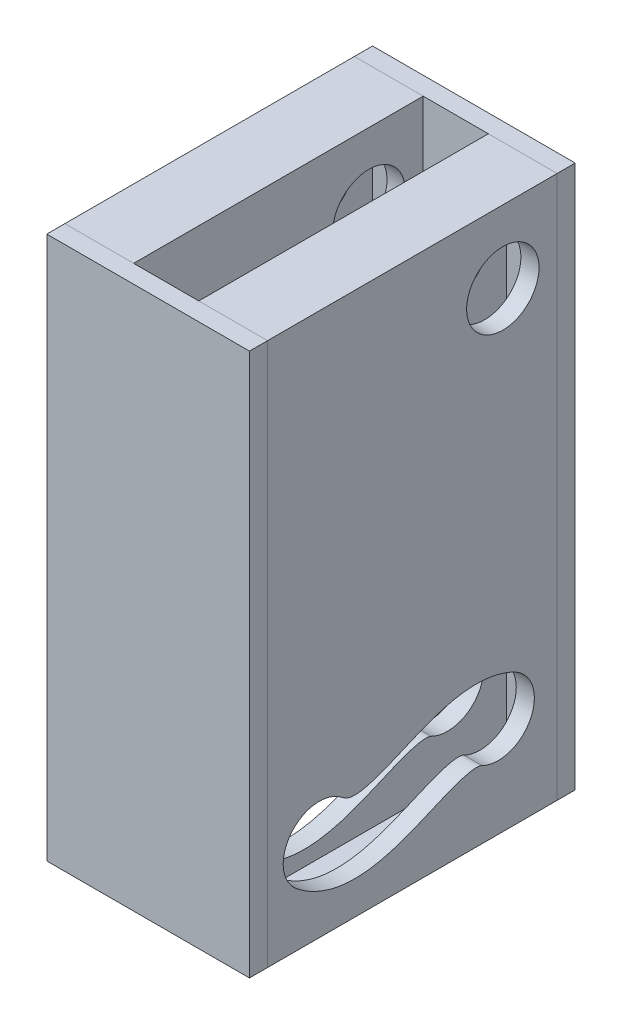
SolidWorks part; units mm, degrees
ref_plane "Front Plane" through (0, 0, 0) normal (0, 0, 1) x (1, 0, 0)
ref_plane "Top Plane" through (0, 0, 0) normal (0, 1, 0) x (1, 0, 0)
ref_plane "Right Plane" through (0, 0, 0) normal (1, 0, 0) x (0, 0, -1)
sketch "Sketch1" plane through (0, 0, 0) normal (0, 0, 1) x (1, 0, 0)
  line L0 (-9, 75) -> (-9, 35)
  line L8 (-9, -35) -> (-9, -75)
  line L9 (-9, -75) -> (-28, -75)
  line L10 (-28, -75) -> (-28, 75)
  line L11 (-28, 75) -> (-9, 75)
  line L12 (0, 171.0434) -> (0, -171.0434) construction
  line L13 (-9, 35) -> (9, 35)
  line L14 (-9, -35) -> (9, -35)
  line L15 (9, -35) -> (9, -75)
  line L16 (9, -75) -> (28, -75)
  line L17 (28, -75) -> (28, 75)
  line L18 (9, 75) -> (9, 35)
  line L19 (28, 75) -> (9, 75)
  line L20 (-23, 70) -> (-14, 70)
  line L21 (-14, 70) -> (-14, 30)
  line L22 (-14, 30) -> (14, 30)
  line L23 (14, 70) -> (14, 30)
  line L24 (23, 70) -> (14, 70)
  line L25 (23, -70) -> (23, 70)
  line L26 (14, -70) -> (23, -70)
  line L27 (14, -30) -> (14, -70)
  line L28 (-14, -30) -> (14, -30)
  line L29 (-14, -30) -> (-14, -70)
  line L30 (-14, -70) -> (-23, -70)
  line L31 (-23, -70) -> (-23, 70)
  line L32 (-66.2515, 55) -> (66.2515, 55) construction
  line L33 (-23, 0) -> (23, 0) construction
  line L34 (-28, 65) -> (28, 65) construction
  line L35 (-28, -65) -> (28, -65) construction
  line L36 (-66.2515, -55) -> (66.2515, -55) construction
  point P6 (0, -35)
  point P16 (0, 35)
  point P31 (0, 0)
  point P34 (0, 55)
  point P35 (-9, 55)
  dimension "D2" = 10
  dimension "D3" = 18
  dimension "D4" = 56
  dimension "D5" = 150
  dimension "D6" = 20
  dimension "D1" = 5
sketch "Sketch2" plane through (0, 0, 0) normal (1, 0, 0) x (0, 0, -1)
  line L0 (-30, 0) -> (50, 0) construction
  line L1 (-30, 0) -> (-35, 0) construction
  line L2 (50, 0) -> (55, 0) construction
  dimension "D1" = 80
  dimension "D2" = 5
  dimension "D3" = 50
extrude "Boss-Extrude1" add sketch "Sketch1" along normal up to vertex (30 mm away) and the other way up to vertex (50 mm away) up to point (0, 0, 30) other way up to point (0, 0, -50)
sketch "Sketch3" plane through (0, 0, 0) normal (0, 0, 1) x (1, 0, 0)
  line L1 (-28, -75) -> (28, -75)
  line L2 (-28, -75) -> (-28, 75)
  line L3 (-28, 75) -> (28, 75)
  line L4 (28, -75) -> (28, 75)
  line L5 (-28, -75) -> (28, 75) construction
  line L6 (-28, 75) -> (28, -75) construction
  point P0 (0, 0)
extrude "Boss-Extrude2" add sketch "Sketch3" along normal up to vertex (35 mm away) from vertex separate body up to point (0, 0, 35) starting at point (0, 0, 30)
extrude "Boss-Extrude3" add sketch "Sketch3<2>" against normal up to vertex (55 mm away) from vertex separate body up to point (0, 0, -55) starting at point (0, 0, -50)
sketch "Sketch3<2>" plane through (0, 0, 0) normal (0, 0, 1) x (1, 0, 0) same geometry as "Sketch3"
sketch "Sketch4" plane through (0, 0, 0) normal (1, 0, 0) x (0, 0, -1)
  line L0 (0, 171.0434) -> (0, -171.0434) construction
  line L1 (0, 0) -> (0, 55) construction
  line L2 (0, 55) -> (35, 55) construction
  line L3 (-4.7922, -56.1999) -> (4.7922, -53.8001) construction
  line L5 (-3.6359, -61.0647) -> (6.0647, -58.6359) construction
  line L6 (-3.6359, -61.0647) -> (-6.0647, -51.3641) construction
  line L7 (-6.0647, -51.3641) -> (3.6359, -48.9353) construction
  line L8 (6.0647, -58.6359) -> (3.6359, -48.9353) construction
  line L9 (-3.6359, -61.0647) -> (3.6359, -48.9353) construction
  line L10 (-6.0647, -51.3641) -> (6.0647, -58.6359) construction
  circle A1 centre (0, -55) radius 10 construction
  arc A2 (-21.9612, -60.1535) -> (-9.4142, -44.5787) centre (-15.6877, -52.3661) cw
  arc A3 (29.2096, -56.2677) -> (38.2188, -38.4118) centre (33.7142, -47.3397) ccw
  circle A4 centre (35, 55) radius 10
  spline S0 degree 3 poles (-15.6877, -52.3661) (-0.6676, -64.4663) (19.4244, -40.1299) (33.7142, -47.3397) knots 0 0 0 0 1 1 1 1 construction
  spline S1 degree 1 poles (-21.9612, -60.1535) (29.2096, -56.2677) knots 0 0 1 1 construction
  spline S2 degree 3 poles (-21.9612, -60.1535) (-21.2326, -60.7404) (-19.7049, -61.8467) (-16.5047, -63.6733) (-12.2723, -65.2199) (-7.2245, -65.9156) (-0.896, -65.6402) (6.0756, -63.823) (13.3281, -60.8744) (19.6872, -58.0691) (24.0439, -56.5285) (26.6043, -56.0154) (27.9543, -55.9488) (28.7219, -56.0631) (29.04, -56.1821) (29.2096, -56.2677) knots 0 0 0 0 0.03125 0.0625 0.125 0.1875 0.25 0.375 0.5 0.625 0.75 0.8125 0.875 0.9375 1 1 1 1
  spline S3 degree 1 poles (-9.4142, -44.5787) (38.2188, -38.4118) knots 0 0 1 1 construction
  spline S4 degree 3 poles (-9.4142, -44.5787) (-9.3177, -44.6565) (-9.113, -44.8128) (-8.7501, -45.0598) (-8.3333, -45.2957) (-7.8736, -45.4934) (-7.2533, -45.6849) (-6.3508, -45.8249) (-4.8225, -45.7841) (-2.8135, -45.4329) (0.4161, -44.5109) (5.2569, -42.5771) (11.8945, -39.6457) (18.0981, -37.3535) (23.6968, -36.1642) (28.2903, -35.8349) (32.4283, -36.3113) (35.7677, -37.2971) (37.4231, -38.0103) (38.2188, -38.4118) knots 0 0 0 0 0.015625 0.03125 0.0625 0.09375 0.125 0.1875 0.25 0.3125 0.375 0.5 0.625 0.75 0.8125 0.875 0.9375 0.96875 1 1 1 1
  point P10 (0, -55)
  point P22 (0, -55)
  dimension "D1" = 10
  dimension "D2" = 10
  dimension "D4" = 35
  dimension "D5" = 20
  dimension "D3" = 10
extrude "Cut-Extrude1" cut sketch "Sketch4" against normal through all and the other way through all contours A4 | S4 A2 S2 A3 L8 L5 L6 L7 | L5 L8 L7 L6 region at (0, -50.8563, -8.874) region at (0, 55, -35)
